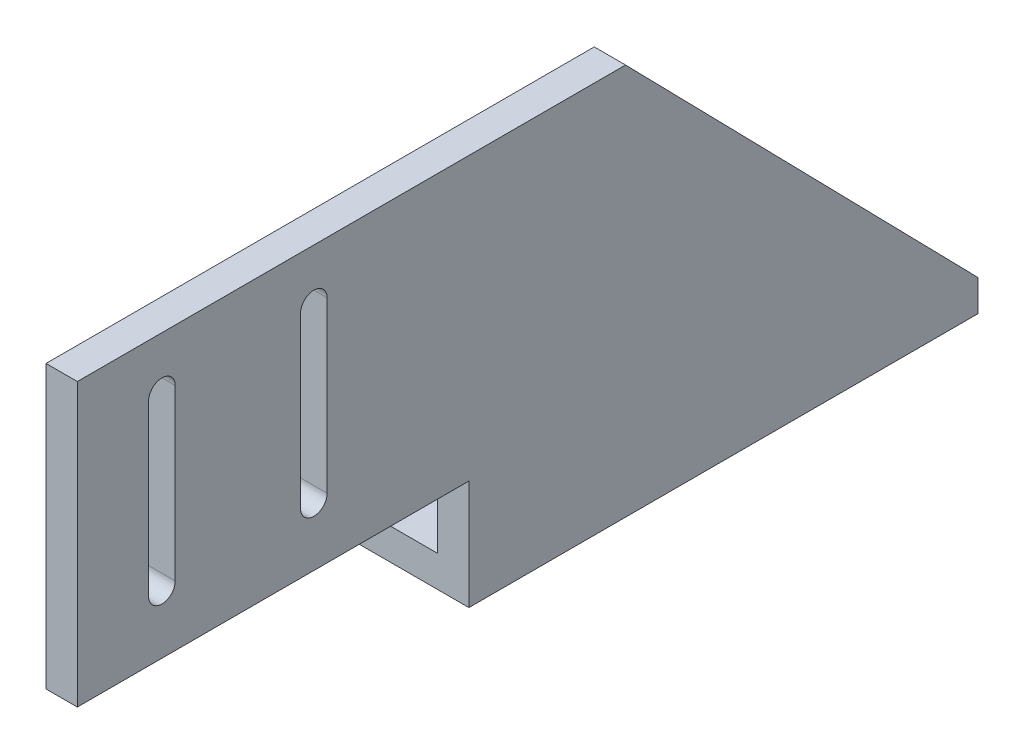
SolidWorks part; units mm, degrees
ref_plane "Front Plane" through (0, 0, 0) normal (1, 0, 0) x (0, 1, 0)
ref_plane "Top Plane" through (0, 0, 0) normal (0, 0, 1) x (0, 1, 0)
ref_plane "Right Plane" through (0, 0, 0) normal (0, 1, 0) x (-1, 0, 0)
sketch "Sketch1" plane through (0, 0, 0) normal (0, 0, 1) x (0, 1, 0)
  line L0 (0, 0) -> (0, -15)
  line L1 (0, -15) -> (23, -15)
  line L2 (23, -15) -> (23, -17)
  line L3 (23, -17) -> (-2, -17)
  line L4 (-2, -17) -> (-2, 0)
  line L5 (-2, 0) -> (0, 0)
  dimension "D1" = 15
  dimension "D2" = 2
  dimension "D3" = 25
extrude "Boss-Extrude1" add sketch "Sketch1" along normal blind 32.5
sketch "Sketch2" plane through (0, -2, 0) normal (0, -1, 0) x (1, 0, 0)
  line L0 (0, 0) -> (17, 0) construction
  line L1 (0, 32.5) -> (0, 0) construction
  line L3 (7, 25) -> (9, 25) construction
  line L4 (7, 27.75) -> (9, 27.75)
  line L5 (7, 22.25) -> (9, 22.25)
  line L6 (7, 7) -> (9, 7) construction
  line L7 (7, 9.75) -> (9, 9.75)
  line L8 (7, 4.25) -> (9, 4.25)
  arc A2 (7, 27.75) -> (7, 22.25) centre (7, 25) ccw
  arc A3 (9, 22.25) -> (9, 27.75) centre (9, 25) ccw
  arc A4 (7, 9.75) -> (7, 4.25) centre (7, 7) ccw
  arc A5 (9, 4.25) -> (9, 9.75) centre (9, 7) ccw
  point P12 (8, 25)
  point P17 (8, 7)
  point P24 (0, 0)
  dimension "D1" = 25
  dimension "D4" = 5.5
  dimension "D5" = 2
  dimension "D6" = 8
  dimension "D7" = 18
extrude "Cut-Extrude1" cut sketch "Sketch2" against normal up to surface (2 mm away) up to face at (7.5, 0, 16.25)
sketch "Sketch3" plane through (17, 0, 0) normal (1, 0, 0) x (0, 1, 0)
  line L0 (23, 22.5) -> (0, 0)
  line L7 (23, 32.5) -> (23, 0) construction
  line L8 (23, 22.5) -> (23, 0)
  line L9 (23, 0) -> (0, 0)
  dimension "D1" = 10
extrude "Cut-Extrude2" cut sketch "Sketch3" against normal blind 2
sketch "Sketch4" plane through (17, 0, 0) normal (1, 0, 0) x (0, 1, 0)
  line L0 (23, 32.5) -> (23, 22.5) construction
  line L1 (-2, 32.5) -> (23, 32.5)
  line L2 (-2, 32.5) -> (-2, 57.5)
  line L3 (-2, 57.5) -> (23, 57.5)
  line L4 (23, 32.5) -> (23, 57.5)
  dimension "D1" = 25
extrude "Boss-Extrude2" add sketch "Sketch4" against normal blind 2
sketch "Sketch5" plane through (17, 0, 0) normal (1, 0, 0) x (0, 1, 0)
  line L0 (8.85, 52.1) -> (19.65, 52.1) construction
  line L3 (8.85, 52.95) -> (19.65, 52.95)
  line L4 (8.85, 51.25) -> (19.65, 51.25)
  line L5 (8.85, 42.4) -> (19.65, 42.4) construction
  line L6 (8.85, 43.25) -> (19.65, 43.25)
  line L7 (8.85, 41.55) -> (19.65, 41.55)
  line L8 (23, 57.5) -> (-2, 57.5) construction
  line L11 (23, 57.5) -> (23, 22.5) construction
  line L15 (-2, 57.5) -> (-2, 0) construction
  arc A2 (8.85, 52.95) -> (8.85, 51.25) centre (8.85, 52.1) ccw
  arc A3 (19.65, 51.25) -> (19.65, 52.95) centre (19.65, 52.1) ccw
  arc A4 (8.85, 43.25) -> (8.85, 41.55) centre (8.85, 42.4) ccw
  arc A5 (19.65, 41.55) -> (19.65, 43.25) centre (19.65, 42.4) ccw
  point P4 (14.25, 52.1)
  point P15 (14.25, 42.4)
  dimension "D1" = 8
  dimension "D2" = 5.4
  dimension "D3" = 2.5
  dimension "D4" = 10
  dimension "D5" = 1.7
extrude "Cut-Extrude3" cut sketch "Sketch5" against normal up to next
sketch "Sketch7" plane through (17, 0, 0) normal (1, 0, 0) x (0, 1, 0)
  line L3 (-2, 32.5) -> (0, 32.5) construction
  line L6 (-2, 32.5) -> (0, 32.5)
  line L8 (-2, 57.5) -> (5, 57.5)
  line L9 (-2, 57.5) -> (-2, 32.5)
  line L12 (5, 32.5) -> (0, 32.5)
  line L13 (5, 57.5) -> (5, 32.5)
  dimension "D1" = 7
extrude "Cut-Extrude4" cut sketch "Sketch7" against normal up to next
